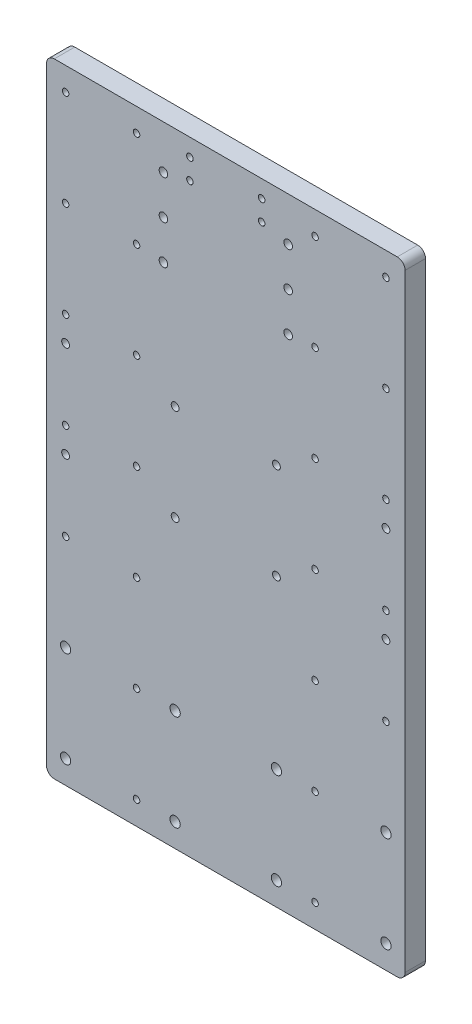
SolidWorks part; units mm, degrees
ref_plane "Front Plane" through (0, 0, 0) normal (0, 0, 1) x (1, 0, 0)
ref_plane "Top Plane" through (0, 0, 0) normal (0, 1, 0) x (1, 0, 0)
ref_plane "Right Plane" through (0, 0, 0) normal (1, 0, 0) x (0, 0, -1)
sketch "Sketch1" plane through (0, 0, 0) normal (0, 0, 1) x (1, 0, 0)
  line L1 (115, 200) -> (-115, 200)
  line L2 (115, 200) -> (115, -200)
  line L3 (115, -200) -> (-115, -200)
  line L4 (-115, 200) -> (-115, -200)
  line L5 (115, 200) -> (-115, -200) construction
  line L6 (115, -200) -> (-115, 200) construction
  point P0 (0, 0)
  dimension "D1" = 230
  dimension "D2" = 400
extrude "Boss-Extrude1" add sketch "Sketch1" along normal blind 13.1
fillet "Fillet1" radius 5 4 edges at (-115, 200, 6.55) (115, -200, 6.55) (-115, -200, 6.55) (115, 200, 6.55)
sketch "Sketch2" plane through (0, 0, 13.1) normal (0, 0, 1) x (1, 0, 0)
  line L1 (-23, 188.85) -> (23, 188.85) construction
  line L2 (-23, 188.85) -> (-23, 175.85) construction
  line L3 (-23, 175.85) -> (23, 175.85) construction
  line L4 (23, 188.85) -> (23, 175.85) construction
  circle A0 centre (-23, 188.85) radius 2.1
  circle A1 centre (23, 188.85) radius 2.1
  circle A2 centre (23, 175.85) radius 2.1
  circle A3 centre (-23, 175.85) radius 2.1
  dimension "D1" = 4.2
extrude "Cut-Extrude1" cut sketch "Sketch2" against normal through all
sketch "Sketch3" plane through (0, 0, 0) normal (0, 0, -1) x (-1, 0, 0)
  line L0 (0, 0) -> (0, 299.0074) construction
  line L1 (-40, 171.9865) -> (-40, 146.9865) construction
  line L2 (-40, 146.9865) -> (-40, 121.9865) construction
  line L3 (-40, 121.9865) -> (0, 121.9865) construction
  circle A0 centre (-40, 121.9865) radius 2.75
  circle A1 centre (-40, 146.9865) radius 2.75
  circle A2 centre (-40, 171.9865) radius 2.75
  circle A3 centre (40, 121.9865) radius 2.75
  circle A4 centre (40, 146.9865) radius 2.75
  circle A5 centre (40, 171.9865) radius 2.75
  dimension "D1" = 5.5
extrude "Cut-Extrude2" cut sketch "Sketch3" against normal through all
sketch "Sketch4" plane through (0, 0, 13.1) normal (0, 0, 1) x (1, 0, 0)
  line L0 (0, 200) -> (0, -200) construction
  line L1 (110, 200) -> (-110, 200) construction
  line L2 (-110, -200) -> (110, -200) construction
  line L3 (102.75, -61.6667) -> (102.75, -123.3333) construction
  line L4 (102.75, -123.3333) -> (102.75, -185) construction
  line L5 (102.75, -185) -> (57.25, -185) construction
  line L6 (57.25, -185) -> (-57.25, -185) construction
  line L7 (-57.25, -185) -> (-102.75, -185) construction
  line L8 (-102.75, -123.3333) -> (-57.25, -123.3333) construction
  line L9 (-57.25, -123.3333) -> (57.25, -123.3333) construction
  line L10 (57.25, -123.3333) -> (102.75, -123.3333) construction
  circle A0 centre (-102.75, 185) radius 2.1
  circle A1 centre (-102.75, 123.3333) radius 2.1
  circle A2 centre (-102.75, 61.6667) radius 2.1
  circle A3 centre (-102.75, 0) radius 2.1
  circle A4 centre (-102.75, -61.6667) radius 2.1
  circle A5 centre (-102.75, -123.3333) radius 3.3
  circle A6 centre (-102.75, -185) radius 3.3
  circle A7 centre (-57.25, 185) radius 2.1
  circle A8 centre (-57.25, 123.3333) radius 2.1
  circle A9 centre (-57.25, 61.6667) radius 2.1
  circle A10 centre (-57.25, 0) radius 2.1
  circle A11 centre (-57.25, -61.6667) radius 2.1
  circle A12 centre (-57.25, -123.3333) radius 2.1
  circle A13 centre (-57.25, -185) radius 2.1
  circle A14 centre (57.25, -185) radius 2.1
  circle A15 centre (57.25, -123.3333) radius 2.1
  circle A16 centre (57.25, -61.6667) radius 2.1
  circle A17 centre (57.25, 0) radius 2.1
  circle A18 centre (57.25, 61.6667) radius 2.1
  circle A19 centre (57.25, 123.3333) radius 2.1
  circle A20 centre (57.25, 185) radius 2.1
  circle A21 centre (102.75, -185) radius 3.3
  circle A22 centre (102.75, -123.3333) radius 3.3
  circle A23 centre (102.75, -61.6667) radius 2.1
  circle A24 centre (102.75, 0) radius 2.1
  circle A25 centre (102.75, 61.6667) radius 2.1
  circle A26 centre (102.75, 123.3333) radius 2.1
  circle A27 centre (102.75, 185) radius 2.1
  dimension "D1" = 4.2
  dimension "D2" = 6.6
extrude "Cut-Extrude3" cut sketch "Sketch4" against normal through all
sketch "Sketch6" plane through (0, 0, 13.1) normal (0, 0, 1) x (1, 0, 0)
  line L0 (-57.25, -123.3333) -> (57.25, -123.3333) construction
  line L1 (-32.5, -123.3333) -> (-32.5, -185) construction
  line L2 (32.5, -123.3333) -> (32.5, -185) construction
  line L3 (-57.25, -185) -> (57.25, -185) construction
  line L4 (0, -60.963) -> (0, -151.8475) construction
  line L5 (-32.5, -123.3333) -> (0, -123.3333) construction
  line L6 (102.75, 61.6667) -> (102.75, -61.6667) construction
  line L7 (0, -123.3333) -> (32.5, -123.3333) construction
  line L8 (32.5, -16.08) -> (102.75, -16.08) construction
  line L9 (32.5, 45.5867) -> (102.75, 45.5867) construction
  line L10 (32.5, 45.5867) -> (32.5, -123.3333) construction
  circle A11 centre (32.5, -123.3333) radius 3.3
  circle A12 centre (-32.5, -123.3333) radius 3.3
  circle A19 centre (-32.5, -185) radius 3.3
  circle A20 centre (32.5, -185) radius 3.3
  circle A25 centre (102.75, 45.5867) radius 2.5
  circle A26 centre (102.75, -16.08) radius 2.5
  circle A27 centre (-102.75, -16.08) radius 2.5
  circle A28 centre (-102.75, 45.5867) radius 2.5
  circle A29 centre (32.5, 45.5867) radius 2.5
  circle A30 centre (32.5, -16.08) radius 2.5
  circle A31 centre (-32.5, -16.08) radius 2.5
  circle A32 centre (-32.5, 45.5867) radius 2.5
  dimension "D2" = 6.6
  dimension "D5" = 5
  dimension "D1" = 65
  dimension "D4" = 168.92
  dimension "D3" = 61.6667
extrude "Cut-Extrude4" cut sketch "Sketch6" against normal through all
equation "\"M5_Thread\"= 4.2mm"
equation "\"M5_Pass\"= 5.5"
equation "\"M6_Thread\"= 5mm"
equation "\"M6_Pass\"= 6.6"
equation "\"M5_Head\"= 9mm"
equation "\"M6_Head\"= 10.5"
equation "\"M5_HeadDepth\"= 5.5"
equation "\"M6_HeadDepth\"= 5.9 + .5"
equation "\"D1@Sketch2\"=\"M5_Thread\""
equation "\"D1@Sketch3\"=\"M5_Pass\""
equation "\"D1@Sketch4\"=\"M5_Thread\""
equation "\"D2@Sketch4\"=\"M6_Pass\""
equation "\"D2@Sketch6\"=\"M6_Pass\""
equation "\"D5@Sketch6\"=\"M6_Thread\""
